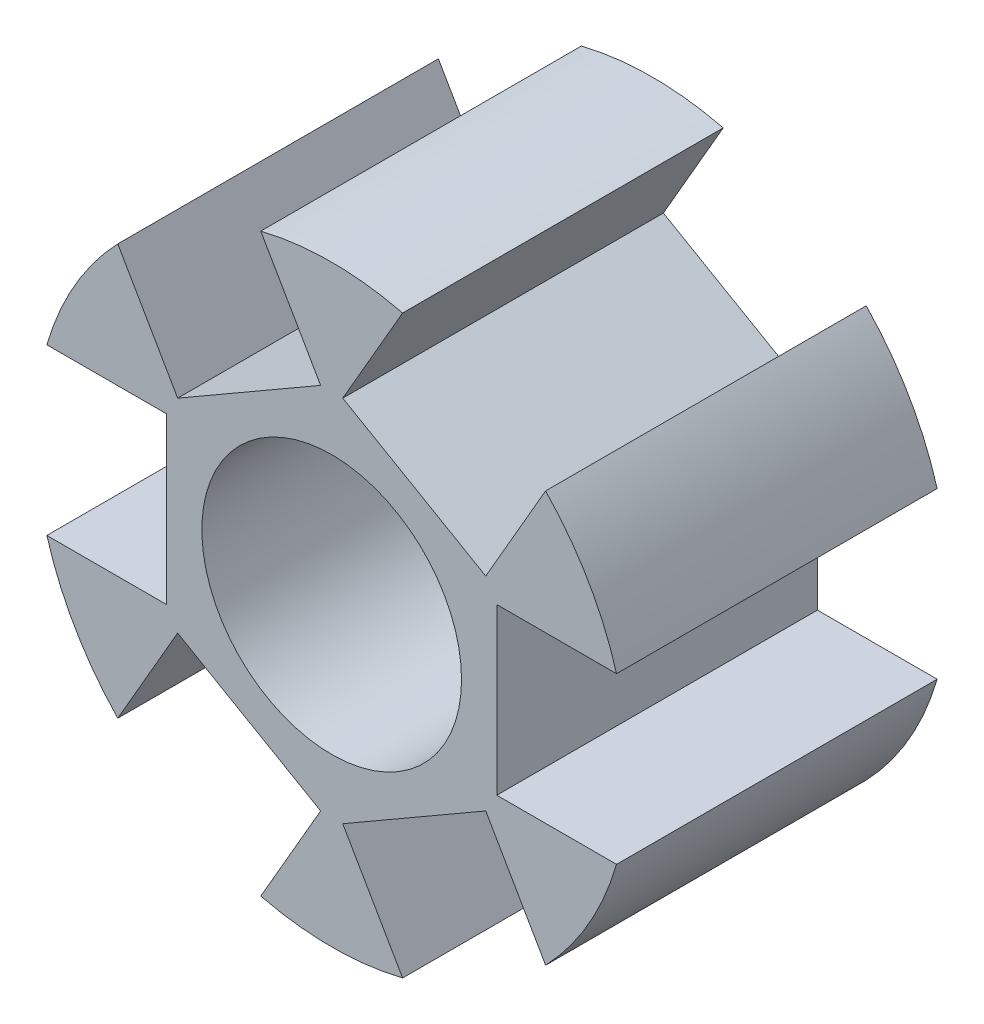
SolidWorks part; units mm, degrees
ref_plane "Top Plane" through (0, 0, 0) normal (0, 0, 1) x (1, 0, 0)
ref_plane "Right Plane" through (0, 0, 0) normal (0, 1, 0) x (1, 0, 0)
ref_plane "Front Plane" through (0, 0, 0) normal (1, 0, 0) x (0, 0, -1)
ref_axis "x-axis" through (-88.99, 0, 0) along (1, 0, 0)
ref_axis "y-axis" through (0, -55, 0) along (0, 1, 0)
ref_axis "z-axis" through (0, 0, 55) along (0, 0, -1)
sketch "Sketch1" plane through (0, 0, 0) normal (0, 0, 1) x (1, 0, 0)
  line L8 (-19.9785, 0) -> (0, 0) construction
  line L16 (0, 0) -> (0, -20.7846) construction
  line L23 (0, 0) -> (0, -20.7846) construction
  circle A0 centre (0, 0) radius 4.05
  circle A3 centre (0, 0) radius 9.25
  dimension "D1" = 8.1
  dimension "D2" = 18.5
extrude "Boss-Extrude1" add sketch "Sketch1" along normal mid plane 10
ref_plane "Plane1" through (-9.25, 0, 0) normal (-1, 0, 0) x (0, 0, 1)
sketch "Sketch2" plane through (-9.25, -17.1931, 0) normal (1, 0, 0) x (0, -1, 0)
  line L1 (-19.7681, -5) -> (-14.6181, -5)
  line L2 (-19.7681, -5) -> (-19.7681, 5)
  line L3 (-19.7681, 5) -> (-14.6181, 5)
  line L4 (-14.6181, -5) -> (-14.6181, 5)
  line L5 (-19.7681, -5) -> (-14.6181, 5) construction
  line L6 (-19.7681, 5) -> (-14.6181, -5) construction
  point P0 (-17.1931, 0)
  dimension "D1" = 5.15
  dimension "D2" = 10
extrude "Cut-Extrude3" cut sketch "Sketch2" along normal blind 4.1
pattern_circular "CirPattern1" count 6 over 360 about axis through (0, 0, 5) along (0, 0, 1) of "Cut-Extrude3"
